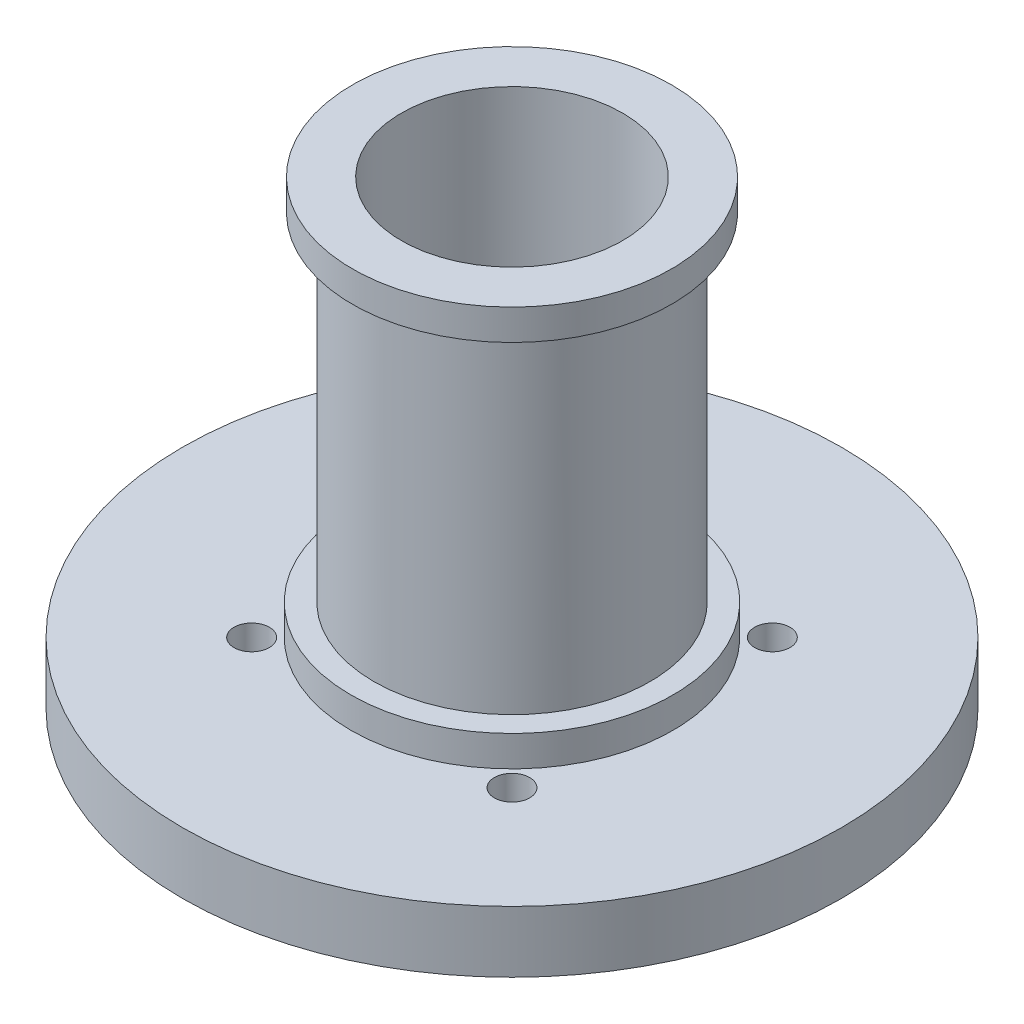
SolidWorks part; units mm, degrees
material "6061 Alloy"
ref_plane "Front Plane" through (0, 0, 0) normal (0, 0, 1) x (1, 0, 0)
ref_plane "Top Plane" through (0, 0, 0) normal (0, 1, 0) x (1, 0, 0)
ref_plane "Right Plane" through (0, 0, 0) normal (1, 0, 0) x (0, 0, -1)
sketch "Sketch1" plane through (0, 0, 0) normal (0, 0, 1) x (1, 0, 0)
  line L0 (0, 0) -> (0, 50.8) construction
  line L1 (11.4458, 50.8) -> (11.4458, 0)
  line L2 (11.4458, 0) -> (14.2875, 0)
  line L3 (14.2875, 0) -> (14.2875, 47.625)
  line L4 (14.2875, 47.625) -> (16.51, 47.625)
  line L5 (16.51, 47.625) -> (16.51, 50.8)
  line L6 (16.51, 50.8) -> (11.4458, 50.8)
  dimension "D1" = 50.8
  dimension "D2" = 28.575
  dimension "D3" = 22.8916
  dimension "D4" = 33.02
  dimension "D5" = 3.175
revolve "Axle" add sketch "Sketch1" angle 360 about L0
sketch "Sketch2" plane through (0, 0, 0) normal (0, 0, 1) x (1, 0, 0)
  line L0 (14.2875, 9.525) -> (14.2875, 6.35)
  line L1 (14.2875, 0) -> (14.2875, 47.625) construction
  line L2 (14.2875, 9.525) -> (34.0995, 9.525)
  line L3 (34.0995, 9.525) -> (34.0995, 3.175)
  line L4 (34.0995, 3.175) -> (30.9245, 3.175)
  line L5 (30.9245, 3.175) -> (30.9245, 6.35)
  line L6 (30.9245, 6.35) -> (14.2875, 6.35)
  line L7 (0, 0) -> (0, 9.525) construction
  dimension "D1" = 6.35
  dimension "D2" = 68.199
  dimension "D3" = 3.175
  dimension "D4" = 3.175
  dimension "D5" = 6.35
revolve "Gear" add sketch "Sketch2" angle 360 about L7
sketch "Sketch3" plane through (0, 0, 0) normal (0, 0, 1) x (1, 0, 0)
  line L0 (0, 0) -> (0, 12.7) construction
  line L2 (14.2875, 9.525) -> (16.6687, 9.525)
  line L3 (14.2875, 9.525) -> (14.2875, 12.7)
  line L4 (14.2875, 12.7) -> (16.6687, 12.7)
  line L5 (16.6687, 9.525) -> (16.6687, 12.7)
  dimension "D1" = 2.3813
  dimension "D2" = 3.175
revolve "Spacer" add sketch "Sketch3" angle 360 about L0
sketch "Sketch4" plane through (0, 6.35, 0) normal (0, -1, 0) x (1, 0, 0)
  line L0 (0, 0) -> (0, -22.9362) construction
  line L1 (-13.4704, -13.4704) -> (13.4704, -13.4704) construction
  line L2 (-13.4704, -13.4704) -> (-13.4704, 13.4704) construction
  line L3 (-13.4704, 13.4704) -> (13.4704, 13.4704) construction
  line L4 (13.4704, -13.4704) -> (13.4704, 13.4704) construction
  line L5 (-13.4704, -13.4704) -> (13.4704, 13.4704) construction
  line L6 (-13.4704, 13.4704) -> (13.4704, -13.4704) construction
  line L7 (16.637, -16.637) -> (-16.637, -16.637) construction
  line L8 (16.637, -16.637) -> (16.637, 16.637) construction
  line L9 (16.637, 16.637) -> (-16.637, 16.637) construction
  line L10 (-16.637, -16.637) -> (-16.637, 16.637) construction
  line L11 (16.637, -16.637) -> (-16.637, 16.637) construction
  line L12 (16.637, 16.637) -> (-16.637, -16.637) construction
  line L13 (-6.35, -22.9362) -> (6.35, -22.9362)
  line L14 (-6.35, -22.9362) -> (-6.35, -17.4633)
  line L15 (6.35, -22.9362) -> (6.35, -17.4633)
  circle A0 centre (0, 0) radius 14.2875
  circle A1 centre (0, 0) radius 14.2875 construction
  arc A2 (-7.3892, 14.906) -> (7.3892, 14.906) centre (0, 0) cw
  circle A3 centre (13.4704, 13.4704) radius 1.8288
  arc A4 (11.133, 15.6068) -> (15.6068, 11.133) centre (13.4704, 13.4704) cw
  arc A5 (7.3892, 14.906) -> (11.133, 15.6068) centre (8.7956, 17.7432) ccw
  arc A6 (15.6068, 11.133) -> (14.906, 7.3892) centre (17.7432, 8.7956) ccw
  arc A7 (14.906, 7.3892) -> (14.906, -7.3892) centre (0, 0) cw
  arc A8 (14.906, -7.3892) -> (15.6068, -11.133) centre (17.7432, -8.7956) ccw
  arc A9 (15.6068, -11.133) -> (11.133, -15.6068) centre (13.4704, -13.4704) cw
  arc A10 (-11.133, -15.6068) -> (-6.35, -17.4633) centre (-9.1018, -17.4633) cw
  arc A11 (11.133, -15.6068) -> (6.35, -17.4633) centre (9.1018, -17.4633) ccw
  circle A12 centre (-13.4704, 13.4704) radius 1.8288
  arc A13 (-11.133, -15.6068) -> (-15.6068, -11.133) centre (-13.4704, -13.4704) cw
  arc A14 (-15.6068, -11.133) -> (-14.906, -7.3892) centre (-17.7432, -8.7956) ccw
  arc A15 (-14.906, -7.3892) -> (-14.906, 7.3892) centre (0, 0) cw
  arc A16 (-14.906, 7.3892) -> (-15.6068, 11.133) centre (-17.7432, 8.7956) ccw
  arc A17 (-15.6068, 11.133) -> (-11.133, 15.6068) centre (-13.4704, 13.4704) cw
  arc A18 (-11.133, 15.6068) -> (-7.3892, 14.906) centre (-8.7956, 17.7432) ccw
  circle A19 centre (-13.4704, -13.4704) radius 1.8288
  arc A20 (7.3892, -14.906) -> (6.35, -15.3775) centre (0, 0) cw [skipped]
  arc A21 (11.133, -15.6068) -> (7.3892, -14.906) centre (8.7956, -17.7432) ccw [skipped]
  arc A22 (-7.3892, -14.906) -> (-11.133, -15.6068) centre (-8.7956, -17.7432) ccw [skipped]
  circle A23 centre (13.4704, -13.4704) radius 1.8288
  point P15 (13.4704, 16.637)
  point P16 (0, 16.637)
  point P50 (0, 0)
  dimension "D2" = 33.274
  dimension "D3" = 3.6576
  dimension "D1" = 38.1
  dimension "D5" = 39.5732
  dimension "D6" = 12.7
  dimension "D4" = 4
extrude "Hub" add sketch "Sketch4" along normal blind 7.62
sketch "Sketch5" plane through (0, 6.35, 0) normal (0, -1, 0) x (1, 0, 0)
  circle A0 centre (-13.4704, 13.4704) radius 1.8288 construction
  circle A1 centre (13.4704, 13.4704) radius 1.8288 construction
  circle A2 centre (13.4704, -13.4704) radius 1.8288 construction
  circle A3 centre (-13.4704, -13.4704) radius 1.8288 construction
  circle A4 centre (-13.4704, 13.4704) radius 1.8288
  circle A5 centre (13.4704, 13.4704) radius 1.8288
  circle A6 centre (13.4704, -13.4704) radius 1.8288
  circle A7 centre (-13.4704, -13.4704) radius 1.8288
extrude "Cut-Extrude1" cut sketch "Sketch5" against normal up to next
